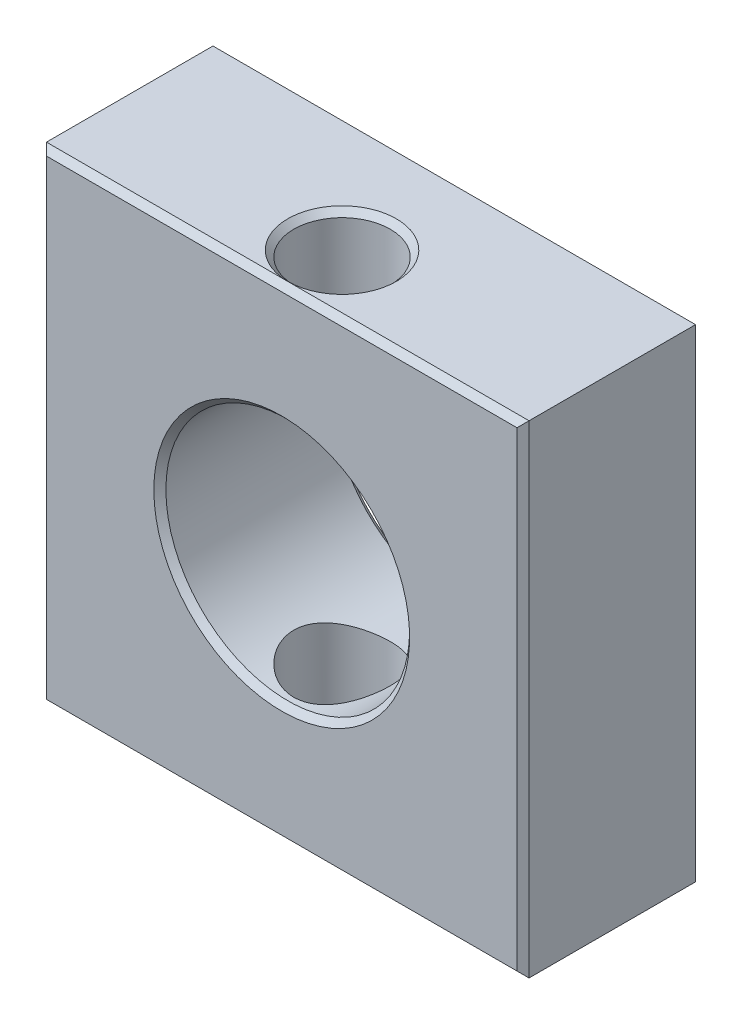
SolidWorks part; units mm, degrees
ref_plane "Front Plane" through (0, 0, 0) normal (0, 0, 1) x (1, 0, 0)
ref_plane "Top Plane" through (0, 0, 0) normal (0, 1, 0) x (1, 0, 0)
ref_plane "Right Plane" through (0, 0, 0) normal (1, 0, 0) x (0, 0, -1)
sketch "Sketch1" plane through (0, 0, 0) normal (0, 0, 1) x (1, 0, 0)
  line L0 (0, 11.646) -> (0, -12.2344) construction
  line L1 (-16.0837, 0) -> (19.3691, 0) construction
  line L3 (-10, -10) -> (10, -10)
  line L4 (-10, -10) -> (-10, 10)
  line L5 (-10, 10) -> (10, 10)
  line L6 (10, -10) -> (10, 10)
  line L7 (-10, -10) -> (10, 10) construction
  line L8 (-10, 10) -> (10, -10) construction
  circle A0 centre (0, 0) radius 5.05
  dimension "D1" = 10.1
  dimension "D2" = 20
  dimension "D3" = 20
extrude "Boss-Extrude1" add sketch "Sketch1" along normal blind 7.4
sketch "Sketch2" plane through (0, 0, 0) normal (0, 1, 0) x (1, 0, 0)
  line L0 (0, 3.8547) -> (0, -9.1116) construction
  line L1 (-11.959, -7.4) -> (12.602, -7.4) construction
  circle A0 centre (0, -4.9) radius 2
  dimension "D2" = 4
  dimension "D3" = 2.5
  dimension "D1" = 7.4
extrude "Cut-Extrude1" cut sketch "Sketch2" against normal through all both and the other way through all
chamfer "Chamfer1" distance 0.25 angle 45 12 edges at (5.05, 0, 7.4) (0, -10, 7.4) (-10, 0, 7.4) (0, 10, 7.4) (10, 0, 7.4) (5.05, 0, 0) (0, 10, 0) (-10, 0, 0) (0, -10, 0) (10, 0, 0) (0, -10, 6.9) (0, 10, 6.9)
